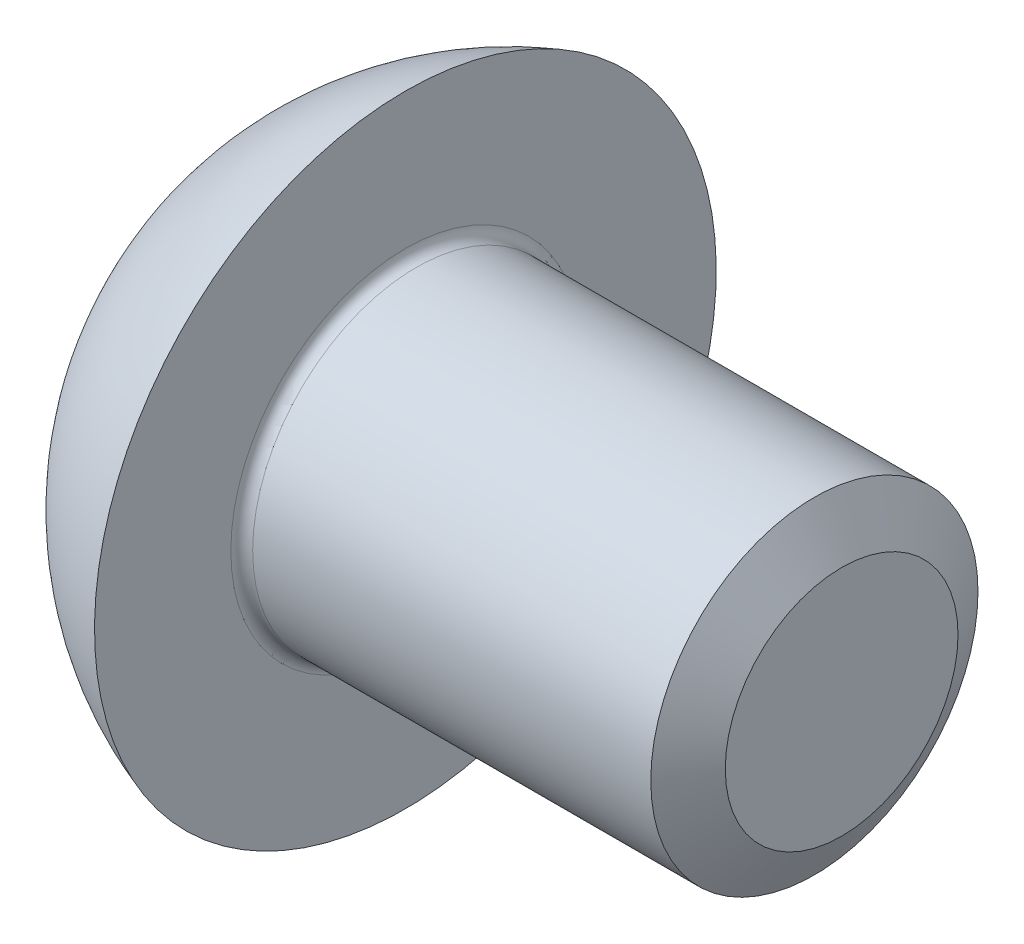
SolidWorks part; units mm, degrees
material "8.8级"
ref_plane "前视基准面" through (0, 0, 0) normal (0, 0, 1) x (1, 0, 0)
ref_plane "上视基准面" through (0, 0, 0) normal (0, 1, 0) x (1, 0, 0)
ref_plane "右视基准面" through (0, 0, 0) normal (1, 0, 0) x (0, 0, -1)
sketch "草图1" plane through (0, 0, 0) normal (0, 0, 1) x (1, 0, 0)
  line L0 (-5.65, 0) -> (0, 0) construction
  line L1 (0, 1.5) -> (-3.9, 1.5)
  line L2 (-4, 1.6) -> (-4, 2.85)
  line L3 (-5.65, 0) -> (-5.65, 1.5)
  line L4 (0, 1.5) -> (0, 0)
  line L5 (-5.65, 0) -> (0, 0)
  arc A0 (-4, 2.85) -> (-5.65, 1.5) centre (-3.0455, 0) ccw
  arc A1 (-3.9, 1.5) -> (-4, 1.6) centre (-3.9, 1.6) cw
  point P10 (-4, 1.5)
  dimension "r" = 0.1
  dimension "d" = 3
  dimension "dk" = 5.7
  dimension "k" = 1.65
  dimension "l" = 4
revolve "旋转1" add sketch "草图1" angle 360 about L0
cosmetic thread "装饰螺纹线1" parameters "D1"=2, "D2"=2.58
sketch "草图2" plane through (-5.65, 0, 0) normal (-1, 0, 0) x (0, 0, 1)
  line L1 (0, 1.1547) -> (-1, 0.5774)
  line L2 (-1, 0.5774) -> (-1, -0.5774)
  line L3 (-1, -0.5774) -> (0, -1.1547)
  line L4 (0, -1.1547) -> (1, -0.5774)
  line L5 (1, -0.5774) -> (1, 0.5774)
  line L6 (1, 0.5774) -> (0, 1.1547)
  circle A0 centre (0, 0) radius 1 construction
  dimension "s" = 2
extrude "切除-拉伸1" cut sketch "草图2" against normal blind 1.65
sketch "草图6" plane through (0, 0, 0) normal (0, 0, 1) x (1, 0, 0)
  line L0 (-4.61, 1.1547) -> (-4, 0)
  line L1 (-3.7, 1.1547) -> (-3.7, 0)
  line L2 (-3.7, 1.1547) -> (-4.61, 1.1547)
  line L3 (-5.65, 0) -> (-4, 0) construction
  line L4 (-3.7, 0) -> (-4, 0)
  line L5 (-5.65, 0) -> (-7.95, 0) construction
  dimension "t" = 1.04
  dimension "e-s" = 0.3
  dimension "k" = 1.65
  dimension "e" = 2.3
revolve "旋转2" add sketch "草图6" angle 360 about L3
sketch "草图7" plane through (0, 0, 0) normal (0, 0, 1) x (1, 0, 0)
  line L3 (-5.65, 1.1547) -> (-5.35, 0)
  line L4 (-5.65, 0) -> (-5.35, 0) construction
  line L7 (-5.65, 1.1547) -> (-5.65, 0)
  line L8 (-5.65, 0) -> (-5.35, 0)
  dimension "e-s" = 0.3
revolve "切除-旋转5" cut sketch "草图7" angle 360 about L4
sketch "草图4" plane through (0, 0, 0) normal (0, 0, 1) x (1, 0, 0)
  line L0 (-0.25, 1.5) -> (0, 1.067)
  line L1 (-0.25, 1.5) -> (0.25, 1.5)
  line L2 (0.25, 1.5) -> (0, 1.067)
  line L4 (0, -1.5) -> (0, 1.5) construction
  line L5 (-0.25, 0) -> (0.25, 0) construction
  dimension "d" = 1.5
  dimension "p" = 0.5
revolve "切除-旋转1" cut sketch "草图4" angle 360 about L5
ref_axis "基准轴1" through (-8.1887, 0, 0) along (1, 0, 0)
pattern_linear "阵列(线性)1" [suppressed] count 4 spacing 0.5 along (-1, 0, 0) of bodies 104
equation "\"D2@装饰螺纹线1\" = \"d@草图1\" * 0.86"
equation "\"k@草图6\" = \"k@切除-拉伸1\""
equation "\"e-s@草图6\" = \"e@草图6\" - \"s@草图2\""
equation "\"e-s@草图7\" = \"e-s@草图6\""
equation "\"d@草图4\" = \"d@草图1\" / 2"
equation "\"k@切除-拉伸1\" = \"k@草图1\""
equation "\"D1@阵列(线性)1\" = \"D1@装饰螺纹线1\" / \"p@草图4\""
equation "\"D3@阵列(线性)1\" = \"p@草图4\""
